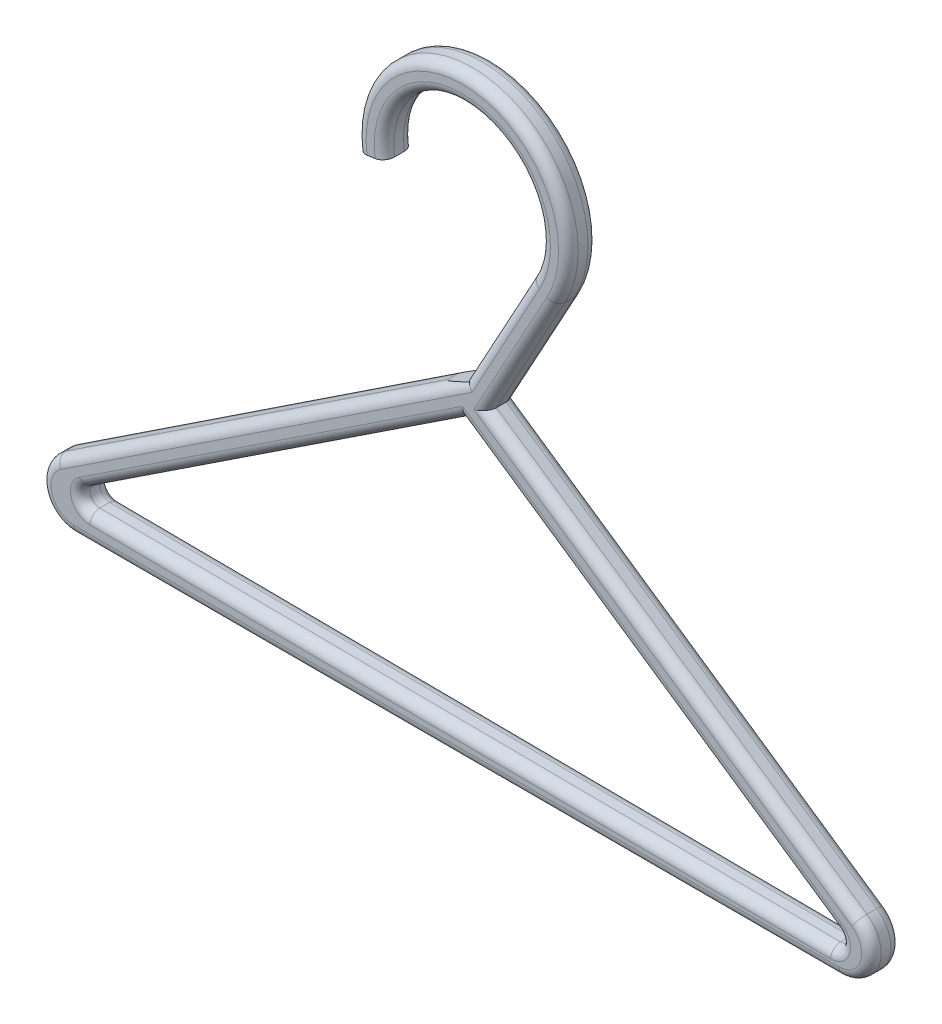
SolidWorks part; units mm, degrees
ref_plane "Plano frontal" through (0, 0, 0) normal (0, 0, 1) x (1, 0, 0)
ref_plane "Plano superior" through (0, 0, 0) normal (0, 1, 0) x (1, 0, 0)
ref_plane "Plano direito" through (0, 0, 0) normal (1, 0, 0) x (0, 0, -1)
sketch "Esboço1" plane through (0, 0, 0) normal (0, 0, 1) x (1, 0, 0)
  line L0 (0, 0) -> (0, -50.042) construction
  line L1 (0, 0) -> (21.0597, -11.5103) construction
  line L2 (21.0597, -11.5103) -> (0, -50.042)
  line L3 (0, 0) -> (-23.7838, -3.214) construction
  line L4 (28.5184, -15.5869) -> (7.4587, -54.1186)
  line L5 (-23.7838, -3.214) -> (-32.2073, -4.3523)
  line L6 (0, -50.042) -> (0, -150.042) construction
  line L7 (-152.2727, -150.042) -> (147.7273, -150.042)
  line L8 (7.4587, -54.1186) -> (147.7273, -150.042)
  line L9 (7.4587, -54.1186) -> (7.4587, 22.8116) construction
  line L10 (7.4587, 22.8116) -> (-7.4587, 22.8116) construction
  line L11 (-7.4587, 22.8116) -> (-7.4587, -54.1186) construction
  line L12 (-152.2727, -150.042) -> (-7.4587, -54.1186)
  line L16 (0, -59.5871) -> (114.627, -137.6979)
  line L17 (-114.1083, -141.5419) -> (112.916, -143.177)
  line L18 (-115.7402, -136.0388) -> (0, -59.5871)
  line L19 (-7.4587, -54.1186) -> (0, -50.042)
  arc A0 (21.0597, -11.5103) -> (-23.7838, -3.214) centre (0, 0) ccw
  arc A1 (28.5184, -15.5869) -> (-32.2073, -4.3523) centre (0, 0) ccw
  arc A4 (-114.1083, -141.5419) -> (-115.7402, -136.0388) centre (-114.0867, -138.542) cw
  arc A5 (114.627, -137.6979) -> (112.916, -143.177) centre (112.9376, -140.177) cw
  dimension "D1" = 48
  dimension "D2" = 38.5317
  dimension "D6" = 300
  dimension "D7" = 169.9311
  dimension "D9" = 3
  dimension "D10" = 3
  dimension "D3" = 8.5
  dimension "D4" = 8.4234
  dimension "D5" = 100
extrude "Ressalto-extrusão1" add sketch "Esboço1" along normal mid plane 9
fillet "Filete1" radius 10 1 edges at (-152.2727, -150.042, 0)
fillet "Filete2" radius 10 1 edges at (147.7273, -150.042, 0)
fillet "Filete6" radius 3 5 edges at (-66.0242, -92.9118, 4.5) (-128.6427, -142.9257, 4.5) (64.2463, -92.9531, 4.5) (124.9427, -142.9963, 4.5) (-1.8392, -150.042, 4.5)
fillet "Filete7" radius 3 5 edges at (64.2463, -92.9531, -4.5) (124.9427, -142.9963, -4.5) (-1.8392, -150.042, -4.5) (-128.6427, -142.9257, -4.5) (-66.0242, -92.9118, -4.5)
fillet "Filete8" radius 3 2 edges at (4.3661, 23.5995, 4.5) (9.3585, -32.9193, 4.5)
fillet "Filete9" radius 3 2 edges at (17.2655, -36.1755, -4.5) (5.9124, 31.9577, -4.5)
fillet "Filete12" radius 3 2 edges at (4.3661, 23.5995, -4.5) (9.3585, -32.9193, -4.5)
fillet "Filete13" radius 3 2 edges at (17.2655, -36.1755, 4.5) (5.9124, 31.9577, 4.5)
fillet "Filete14" radius 3 5 edges at (57.3135, -98.6425, -4.5) (115.8013, -141.0713, -4.5) (-0.5961, -142.3594, -4.5) (-116.9629, -139.3949, -4.5) (-57.8701, -97.813, -4.5)
fillet "Filete15" radius 3 5 edges at (57.3135, -98.6425, 4.5) (115.8013, -141.0713, 4.5) (-0.5961, -142.3594, 4.5) (-116.9629, -139.3949, 4.5) (-57.8701, -97.813, 4.5)
